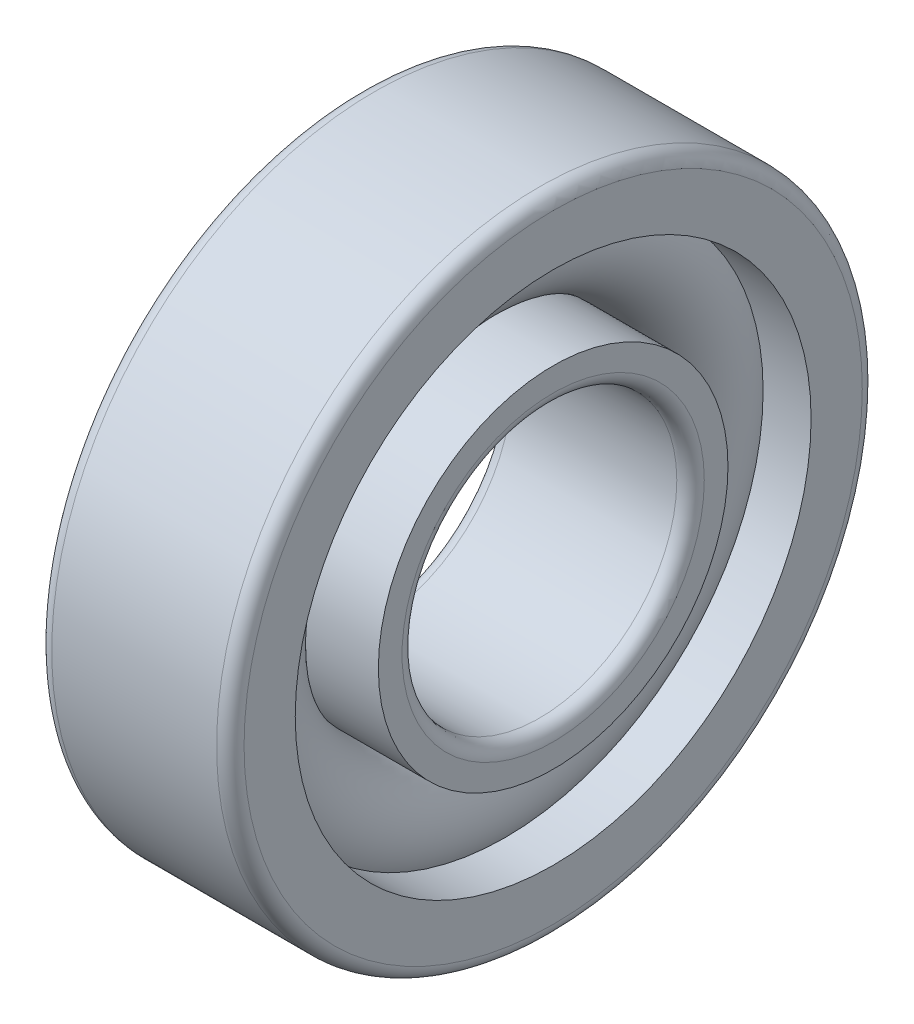
SolidWorks part; units mm, degrees
ref_plane "Plane1" through (0, 0, 0) normal (0, 0, 1) x (1, 0, 0)
ref_plane "Plane2" through (0, 0, 0) normal (0, 1, 0) x (1, 0, 0)
ref_plane "Plane3" through (0, 0, 0) normal (1, 0, 0) x (0, 0, -1)
sketch "Clipboard" plane through (0, 0, 0) normal (0, 0, 1) x (1, 0, 0)
  line L0 (-10, 0) -> (10, 0) construction
  line L1 (0, 0) -> (22.3471, -0.7804)
  line L2 (0, 0) -> (16.7398, 0.5846)
  line L3 (0, 0) -> (22.3471, -0.7804)
  line L4 (0, 0) -> (-22.3573, -0.3902)
  dimension "BallCLRad" = 16.75
sketch "CagSpiSke" plane through (0, 0, 0) normal (0, 0, 1) x (1, 0, 0)
  line L0 (1.0125, 16.075) -> (1.0125, 17.425)
  line L1 (1.0125, 17.425) -> (-1.0125, 17.425)
  line L2 (-1.0125, 17.425) -> (-1.0125, 16.075)
  line L3 (-1.0125, 16.075) -> (1.0125, 16.075)
  line L4 (-20.6375, 0) -> (20.6375, 0) construction
  line L5 (0, 0) -> (0, 23.7692) construction
  dimension "OD" = 34.85
  dimension "ID" = 32.15
revolve "CageSpine" add sketch "CagSpiSke" angle 0.001 about L4
ref_axis "Axis1" through (-50, 0, 0) along (1, 0, 0)
sketch "CagBalSke" plane through (0, 0, 0) normal (0, 0, 1) x (1, 0, 0)
  line L0 (-4.455, 16.75) -> (4.455, 16.75)
  line L1 (-1.905, 16.75) -> (1.905, 16.75) construction
  line L2 (-10, 0) -> (10, 0) construction
  line L3 (0, 0) -> (0, 24) construction
  arc A0 (4.455, 16.75) -> (-4.455, 16.75) centre (0, 16.75) cw
  dimension "BallCLRad" = 16.75
revolve "CageBall" [suppressed] add sketch "CagBalSke" angle 360 about L1 reverse direction yes
pattern_circular "CageBalls" [suppressed] count 2 every 180 about axis through (-50, 0, 0) along (1, 0, 0)
sketch "CagTrmODSke" plane through (0, 0, 0) normal (0, 0, 1) x (1, 0, 0)
  line L0 (4.456, 17.425) -> (4.456, 21.206)
  line L1 (4.456, 21.206) -> (-4.456, 21.206)
  line L2 (-4.456, 21.206) -> (-4.456, 17.425)
  line L3 (-4.456, 17.425) -> (4.456, 17.425)
  line L4 (-20.6375, 0) -> (20.6375, 0) construction
  line L5 (0, 0) -> (0, 25) construction
  dimension "Width" = 8.912
  dimension "ID" = 34.85
  dimension "OD" = 42.412
revolve "CageTrimOD" [suppressed] cut sketch "CagTrmODSke" angle 360 about L4 reverse direction yes
sketch "CagTrmIDSke" plane through (0, 0, 0) normal (0, 0, 1) x (1, 0, 0)
  line L0 (4.456, 12.296) -> (4.456, 16.075)
  line L1 (4.456, 16.075) -> (-4.456, 16.075)
  line L2 (-4.456, 16.075) -> (-4.456, 12.296)
  line L3 (-4.456, 12.296) -> (4.456, 12.296)
  line L4 (-20.6375, 0) -> (20.6375, 0) construction
  line L5 (0, 0) -> (0, 25) construction
  dimension "Width" = 8.912
  dimension "ID" = 24.592
  dimension "OD" = 32.15
revolve "CageTrimID" [suppressed] cut sketch "CagTrmIDSke" angle 360 about L4 reverse direction yes
sketch "BalSimSke" plane through (0, 0, 0) normal (0, 0, 1) x (1, 0, 0)
  line L0 (-10, 0) -> (10, 0) construction
  line L1 (-10, 16.75) -> (10, 16.75) construction
  line L2 (0, 0) -> (0, 23) construction
  circle A0 centre (0, 16.75) radius 4.05
  dimension "BallCLRad" = 16.75
  dimension "Ball_diameter" = 8.1
revolve "BallsSimplified" add sketch "BalSimSke" angle 360 about L0
sketch "BalDetSke" plane through (0, 0, 0) normal (0, 0, 1) x (1, 0, 0)
  line L0 (-4.05, 16.75) -> (4.05, 16.75)
  line L1 (-1.905, 16.75) -> (1.905, 16.75) construction
  line L2 (0, 0) -> (0, 25) construction
  arc A0 (4.05, 16.75) -> (-4.05, 16.75) centre (0, 16.75) cw
  dimension "BallCLRad" = 16.75
  dimension "Ball_diameter" = 8.1
revolve "BallDetailed" [suppressed] add sketch "BalDetSke" angle 360 about L1 reverse direction yes
sketch "InnRacSke" plane through (0, 0, 0) normal (0, 0, 1) x (1, 0, 0)
  line L0 (-3.4785, 14.725) -> (-7, 14.725)
  line L1 (-7, 14.725) -> (-7, 11)
  line L2 (-6, 10) -> (6, 10)
  line L3 (7, 11) -> (7, 12.725)
  line L4 (0, 12.725) -> (7, 12.725)
  line L5 (-20.6375, 0) -> (20.6375, 0) construction
  line L6 (0, 0) -> (0, 30) construction
  arc A0 (-7, 11) -> (-6, 10) centre (-6, 11) ccw
  arc A1 (6, 10) -> (7, 11) centre (6, 11) ccw
  arc A2 (0, 12.725) -> (-3.4785, 14.725) centre (0, 16.75) cw
  dimension "BallCLRad" = 16.75
  dimension "Fillet_radius" = 1
  dimension "Ball_diameter" = 8.05
  dimension "ID" = 20
  dimension "OD" = 29.45
  dimension "Width" = 14
revolve "InnerRace" add sketch "InnRacSke" angle 360 about L5 reverse direction yes
sketch "OutRacSke" plane through (0, 0, 0) normal (0, 0, 1) x (1, 0, 0)
  line L0 (0, 20.775) -> (-7, 20.775)
  line L1 (-7, 20.775) -> (-7, 22.5)
  line L2 (-6, 23.5) -> (6, 23.5)
  line L3 (7, 22.5) -> (7, 18.775)
  line L4 (7, 18.775) -> (3.4785, 18.775)
  line L5 (-20.6375, 0) -> (20.6375, 0) construction
  line L6 (0, 0) -> (0, 30) construction
  arc A0 (-7, 22.5) -> (-6, 23.5) centre (-6, 22.5) cw
  arc A1 (6, 23.5) -> (7, 22.5) centre (6, 22.5) cw
  arc A2 (3.4785, 18.775) -> (0, 20.775) centre (0, 16.75) ccw
  dimension "BallCLRad" = 16.75
  dimension "Fillet_radius" = 1
  dimension "Ball_diameter" = 8.05
  dimension "Width" = 14
revolve "OuterRace" add sketch "OutRacSke" angle 360 about L5 reverse direction yes
pattern_circular "BallsDetailed" [suppressed] count 2 every 180 about axis through (-50, 0, 0) along (1, 0, 0)
equation "\"BallCLRad@Clipboard\" = ( \"OD@OutRacSke\" + \"ID@InnRacSke\" ) / 4"
equation "\"BallCLRad@BalSimSke\" = \"BallCLRad@Clipboard\""
equation "\"BallCLRad@BalDetSke\" = \"BallCLRad@Clipboard\""
equation "\"BallCLRad@InnRacSke\" = \"BallCLRad@Clipboard\""
equation "\"BallCLRad@OutRacSke\" = \"BallCLRad@Clipboard\""
equation "\"Ball_diameter@InnRacSke\" = \"Ball_diameter@BalDetSke\" - 0.05"
equation "\"Ball_diameter@OutRacSke\" = \"Ball_diameter@BalDetSke\" - 0.05"
equation "\"Ball_diameter@BalSimSke\" = \"Ball_diameter@BalDetSke\""
equation "\"Width@OutRacSke\" = \"Width@InnRacSke\""
equation "\"Fillet_radius@OutRacSke\" = \"Fillet_radius@InnRacSke\""
equation "\"Max_count@Clipboard\" = int( 3.14159265 / atn(( \"Ball_diameter@BalDetSke\" / 2) / sqr( \"BallCLRad@Clipboard\"  *  \"BallCLRad@Clipboard\" - ( \"Ball_diameter@BalDetSke\" / 2) *  ( \"Ball_diameter@BalDetSke\" / 2))))"
equation "\"Max_count@Clipboard\" = ((sgn( \"Max_count@Clipboard\" - \"Count@Clipboard\" )-1)*( \"Max_count@Clipboard\" - \"Count@Clipboard\" ))/-2+ \"Count@Clipboard\""
equation "\"Count@BallsDetailed\" = int( \"Show_count@Clipboard\" ) "
equation "\"Count@BallsDetailed\" = ((sgn( \"Count@BallsDetailed\" - \"Max_count@Clipboard\" )-1)*( \"Count@BallsDetailed\" - \"Max_count@Clipboard\" ))/-2+ \"Max_count@Clipboard\""
equation "\"Count@BallsDetailed\" = ((sgn( \"Count@BallsDetailed\" - \"Min_count@Clipboard\" )+1)*( \"Count@BallsDetailed\" - \"Min_count@Clipboard\"))/2 +\"Min_count@Clipboard\""
equation "\"Angle@BallsDetailed\" = 360.0 / \"Max_count@Clipboard\""
equation "\"BallCLRad@CagBalSke\" = \"BallCLRad@Clipboard\""
equation "\"Count@CageBalls\" = \"Count@BallsDetailed\""
equation "\"Angle@CageBalls\" = \"Angle@BallsDetailed\""
equation "\"Angle@CageSpine\" =  \"Angle@CageBalls\" * ( \"Count@CageBalls\" -1 + int( \"Count@CageBalls\" / \"Max_count@Clipboard\" ) )  + 0.001 -  int( \"Count@CageBalls\" / \"Max_count@Clipboard\" ) * 0.001"
equation "\"Angle@CageSpine\" =  \"Angle@CageSpine\" * int( \"Min_count@Clipboard\" / 2) + int(1 / \"Min_count@Clipboard\")  * 0.001"
equation "\"CageWallOD@CagBalSke\" =  \"Ball_diameter@BalDetSke\" * 1.1"
equation "\"Thickness@CagSpiSke\" =  \"Ball_diameter@BalDetSke\" * 0.25"
equation "\"OD@CagTrmODSke\" = \"BallCLRad@Clipboard\" * 2 + \"CageWallOD@CagBalSke\" + 0.002"
equation "\"ID@CagTrmODSke\" = \"BallCLRad@Clipboard\" * 2 + \"Ball_diameter@BalDetSke\" / 6"
equation "\"OD@CagTrmIDSke\" = \"BallCLRad@Clipboard\" * 2 - \"Ball_diameter@BalDetSke\" / 6"
equation "\"ID@CagTrmIDSke\" = \"BallCLRad@Clipboard\" * 2 - \"CageWallOD@CagBalSke\" + 0.002"
equation "\"OD@CagSpiSke\" = \"ID@CagTrmODSke\""
equation "\"ID@CagSpiSke\" = \"OD@CagTrmIDSke\""
equation "\"Width@CagTrmODSke\" = \"CageWallOD@CagBalSke\" + 0.002"
equation "\"Width@CagTrmIDSke\" = \"CageWallOD@CagBalSke\" + 0.002"
